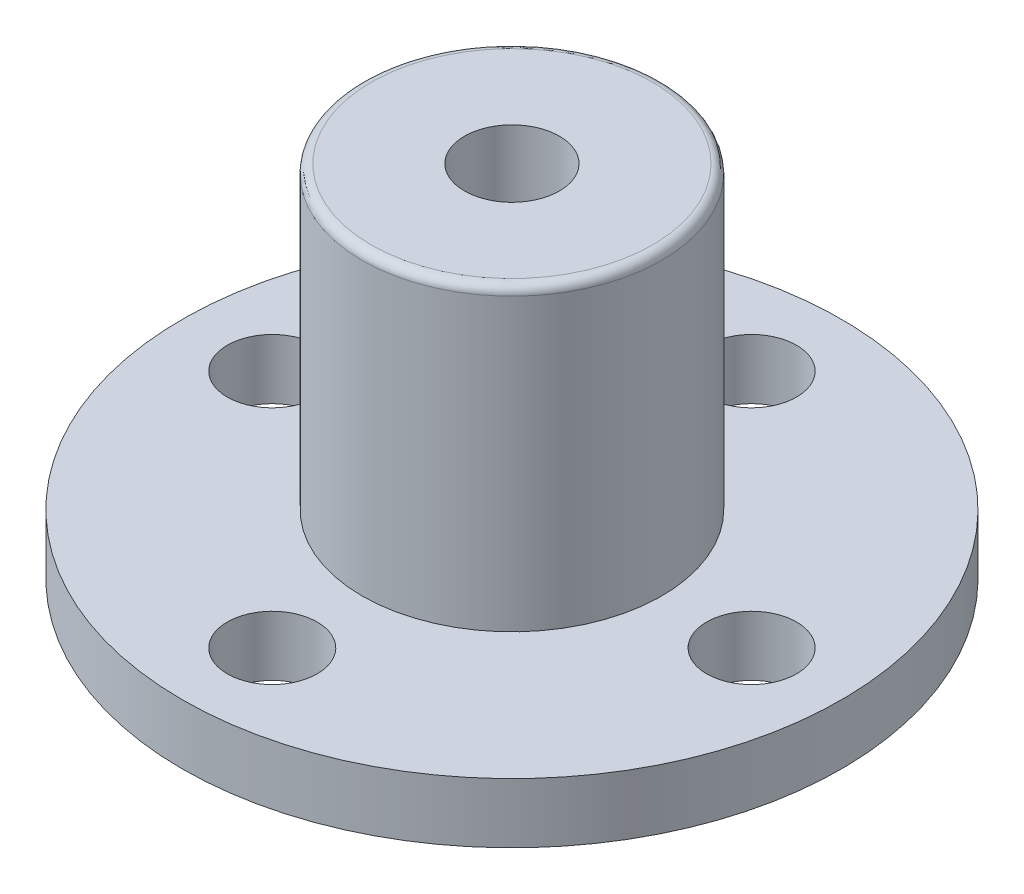
SolidWorks part; units mm, degrees
ref_plane "Front Plane" through (0, 0, 0) normal (0, 0, 1) x (1, 0, 0)
ref_plane "Top Plane" through (0, 0, 0) normal (0, 1, 0) x (1, 0, 0)
ref_plane "Right Plane" through (0, 0, 0) normal (1, 0, 0) x (0, 0, -1)
sketch "Sketch1" plane through (0, 0, 0) normal (0, 1, 0) x (1, 0, 0)
  circle A0 centre (0, 0) radius 11
  dimension "D1" = 22
extrude "Boss-Extrude1" add sketch "Sketch1" along normal blind 2 contours A0
sketch "Sketch2" plane through (0, 2, 0) normal (0, 1, 0) x (1, 0, 0)
  circle A0 centre (0, 0) radius 5
  dimension "D1" = 10
extrude "Boss-Extrude2" add sketch "Sketch2" along normal blind 10
fillet "Fillet1" radius 0.3 1 edges at (0, 12, 5)
sketch "Sketch3" plane through (0, 2, 0) normal (0, 1, 0) x (1, 0, 0)
  circle A0 centre (0, 8) radius 1.5
  circle A1 centre (8, 0) radius 1.5
  circle A2 centre (0, -8) radius 1.5
  circle A3 centre (-8, 0) radius 1.5
  point P11 (0, 0)
  dimension "D1" = 3
  dimension "D2" = 8
  dimension "D3" = 4
extrude "Cut-Extrude1" cut sketch "Sketch3" against normal blind 10
sketch "Sketch4" plane through (0, 12, 0) normal (0, 1, 0) x (1, 0, 0)
  circle A0 centre (0, 0) radius 1.585
  dimension "D1" = 3.17
extrude "Cut-Extrude2" cut sketch "Sketch4" against normal blind 20
ref_axis "Axis1" through (0, 0, -8) along (0, 1, 0)
